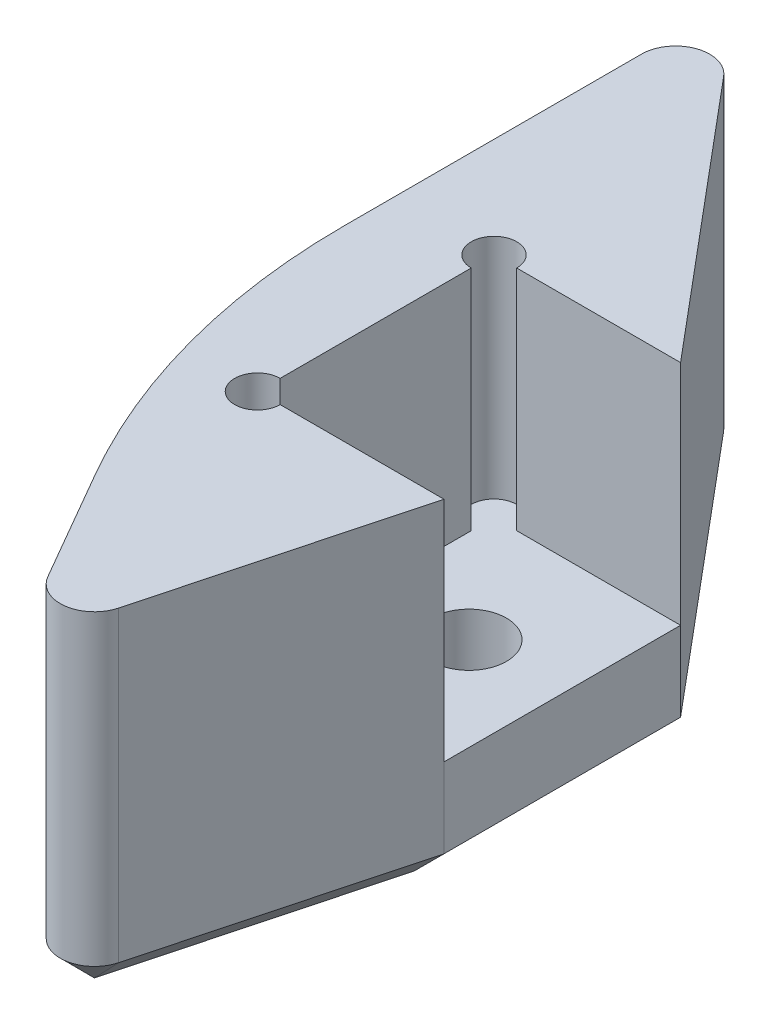
SolidWorks part; units mm, degrees
material "ﾎﾟﾘｴｽﾃﾙ樹脂"
ref_plane "正面" through (0, 0, 0) normal (0, 0, 1) x (1, 0, 0)
ref_plane "平面" through (0, 0, 0) normal (0, 1, 0) x (1, 0, 0)
ref_plane "右側面" through (0, 0, 0) normal (1, 0, 0) x (0, 0, -1)
sketch "ｽｹｯﾁ1" plane through (0, 0, 0) normal (0, 1, 0) x (1, 0, 0)
  line L0 (-4.1, 5.2) -> (8.5, 20.2)
  line L1 (-4, -5) -> (4, -5) construction
  line L2 (-4, -5) -> (-4, 5) construction
  line L3 (-4, 5) -> (4, 5) construction
  line L4 (4, -5) -> (4, 5) construction
  line L5 (-4, -5) -> (4, 5) construction
  line L6 (-4, 5) -> (4, -5) construction
  line L7 (-4.1, -5.2) -> (4.1, -5.2)
  line L8 (-4.1, -5.2) -> (-4.1, 5.2)
  line L9 (-4.1, 5.2) -> (4.1, 5.2)
  line L10 (4.1, -5.2) -> (4.1, 5.2)
  line L11 (-4.1, -5.2) -> (4.1, 5.2) construction
  line L12 (-4.1, 5.2) -> (4.1, -5.2) construction
  line L13 (8.5, 20.2) -> (8.5, -5)
  line L14 (8.5, -5) -> (-0.1603, -20)
  line L15 (-0.1603, -20) -> (-4.1, -5.2)
  line L16 (4, -5) -> (8.5, -5) construction
  circle A0 centre (0, 0) radius 1.65
  point P0 (0, 0)
  dimension "D3" = 3.3
  dimension "D1" = 10
  dimension "D2" = 8
  dimension "D4" = 10.4
  dimension "D5" = 8.2
  dimension "D6" = 4.5
  dimension "D7" = 15
  dimension "D8" = 15
  dimension "D9" = 30
extrude "ﾎﾞｽ - 押し出し1" add sketch "ｽｹｯﾁ1" along normal blind 15 contours L15 L14 L13 L0 L9 L10 L7 | L7 L10 L9 L8 A0 region at (0, 0, -5.0676) region at (2.5226, 0, -12.429)
sketch "ｽｹｯﾁ2" plane through (0, 15, 0) normal (0, 1, 0) x (1, 0, 0)
  line L1 (4.1, -5.2) -> (-4.1, -5.2)
  line L2 (4.1, -5.2) -> (4.1, 5.2)
  line L3 (4.1, 5.2) -> (-4.1, 5.2)
  line L4 (-4.1, -5.2) -> (-4.1, 5.2)
  line L5 (4.1, -5.2) -> (-4.1, 5.2) construction
  line L6 (4.1, 5.2) -> (-4.1, -5.2) construction
  point P0 (0, 0)
extrude "ｶｯﾄ - 押し出し1" cut sketch "ｽｹｯﾁ2" against normal blind 10
fillet "ﾌｨﾚｯﾄ1" radius 30 1 edges at (8.5, 7.5, 5)
fillet "ﾌｨﾚｯﾄ2" radius 1.5 2 edges at (-0.1603, 7.5, 20) (8.5, 7.5, -20.2)
chamfer "面取り1" distance 1.5 angle 45 8 edges at (3.0677, 0, 14.4091) (0.1586, 0, 17.5936) (-2.597, 0, 10.8462) (-4.1, 0, 0) (0.8757, 0, -11.1235) (7.5134, 0, -17.4916) (7.4778, 0, 4.7261) (8.5, 0, -9.5603)
ref_plane "平面1" through (8.5, 0, 0) normal (1, 0, 0) x (0, 0, -1)
mirror "ﾐﾗｰ7" about plane through (8.5, 0, 0) normal (1, 0, 0) of bodies 102
sketch "ｽｹｯﾁ3" plane through (0, 15, 0) normal (0, 1, 0) x (1, 0, 0)
  line L0 (8.5, -55) -> (8.5, 55) construction
  line L1 (8.5, 20.2) -> (-11.5, 20.2)
  line L2 (8.5, 20.2) -> (8.5, -19.8)
  line L3 (8.5, -19.8) -> (-11.5, -19.8)
  line L4 (-11.5, 20.2) -> (-11.5, -19.8)
  line L5 (4.1, 5.2) -> (-4.1, 5.2) construction
  dimension "D1" = 20
  dimension "D2" = 40
  dimension "D3" = 15
extrude "ｶｯﾄ - 押し出し2" cut sketch "ｽｹｯﾁ3" against normal through all
sketch "ｽｹｯﾁ4" plane through (0, 15, 0) normal (0, 1, 0) x (1, 0, 0)
  circle A0 centre (12.9, 5.2) radius 1
  circle A1 centre (12.9, -5.2) radius 1
  dimension "D1" = 2
extrude "ｶｯﾄ - 押し出し3" cut sketch "ｽｹｯﾁ4" against normal up to surface (10 mm away) up to face at (17, 5, 1.65)
